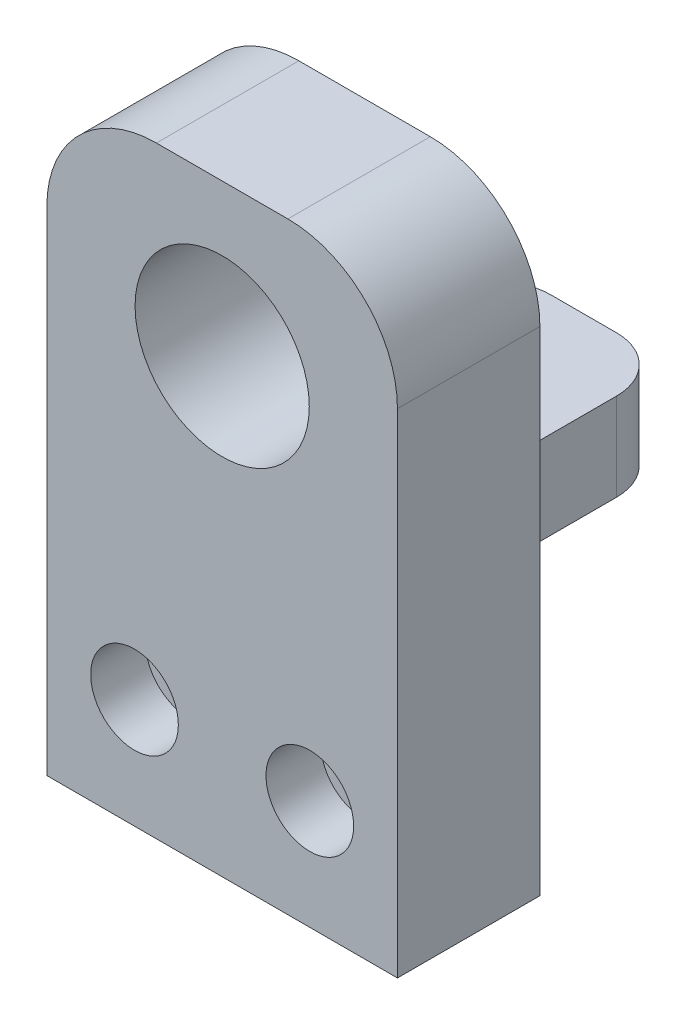
SolidWorks part; units mm, degrees
ref_plane "Alzado" through (0, 0, 0) normal (0, 0, 1) x (1, 0, 0)
ref_plane "Planta" through (0, 0, 0) normal (0, 1, 0) x (1, 0, 0)
ref_plane "Vista lateral" through (0, 0, 0) normal (1, 0, 0) x (0, 0, -1)
sketch "Croquis1" plane through (0, 0, 0) normal (0, 0, 1) x (1, 0, 0)
  line L0 (255, -10) -> (0, -10) construction
  line L1 (111.5, -10) -> (143.5, -10)
  line L2 (111.5, -10) -> (111.5, 45)
  line L3 (111.5, 45) -> (143.5, 45)
  line L4 (143.5, -10) -> (143.5, 45)
  line L5 (127.5, 31.15) -> (127.5, 45) construction
  circle A0 centre (127.5, 31.15) radius 7.95
  circle A1 centre (119.5, 0) radius 2.05
  circle A2 centre (135.5, 0) radius 2.05
  dimension "D1" = 15.9
  dimension "D4" = 4.1
  dimension "D2" = 32
  dimension "D3" = 55
  dimension "D5" = 10
  dimension "D6" = 8
extrude "Saliente-Extruir2" add sketch "Croquis1" along normal blind 13
fillet "Redondeo1" radius 10 2 edges at (111.5, 45, 6.5) (143.5, 45, 6.5)
sketch "Croquis2" plane through (0, 0, 13) normal (0, 0, 1) x (1, 0, 0)
  circle A0 centre (119.5, 0) radius 4
  circle A1 centre (135.5, 0) radius 4
  dimension "D1" = 8
extrude "Cortar-Extruir1" cut sketch "Croquis2" against normal blind 5
sketch "Croquis3" plane through (0, 0, 0) normal (0, 0, -1) x (-1, 0, 0)
  line L0 (-119.5, 10) -> (-135.5, 10) construction
  line L3 (-111.5, -10) -> (-143.5, -10) construction
  line L4 (-143.5, -10) -> (-143.5, 35) construction
  line L5 (-135.5, 10) -> (-119.5, 10)
  line L6 (-135.5, 10) -> (-135.5, 18)
  line L7 (-135.5, 18) -> (-119.5, 18)
  line L8 (-119.5, 10) -> (-119.5, 18)
  line L9 (-111.5, 35) -> (-111.5, -10) construction
  point P10 (0, 0)
  dimension "D1" = 20
  dimension "D2" = 8
  dimension "D3" = 8
  dimension "D4" = 8
extrude "Saliente-Extruir3" add sketch "Croquis3" along normal blind 20
sketch "Croquis4" plane through (0, 18, 0) normal (0, 1, 0) x (1, 0, 0)
  line L0 (127.5, 20) -> (127.5, 10) construction
  line L1 (119.5, 20) -> (135.5, 20) construction
  circle A0 centre (127.5, 10) radius 2.05
  dimension "D1" = 4.1
  dimension "D2" = 10
extrude "Cortar-Extruir2" cut sketch "Croquis4" against normal up to next
sketch "Croquis5" plane through (0, 18, 0) normal (0, 1, 0) x (1, 0, 0)
  circle A0 centre (127.5, 10) radius 4
  dimension "D1" = 8
extrude "Cortar-Extruir3" cut sketch "Croquis5" against normal blind 3
fillet "Redondeo3" radius 8 3 edges at (119.5, 14, 0) (127.5, 18, 0) (135.5, 14, 0)
fillet "Redondeo4" radius 5 2 edges at (119.5, 14, -20) (135.5, 14, -20)
